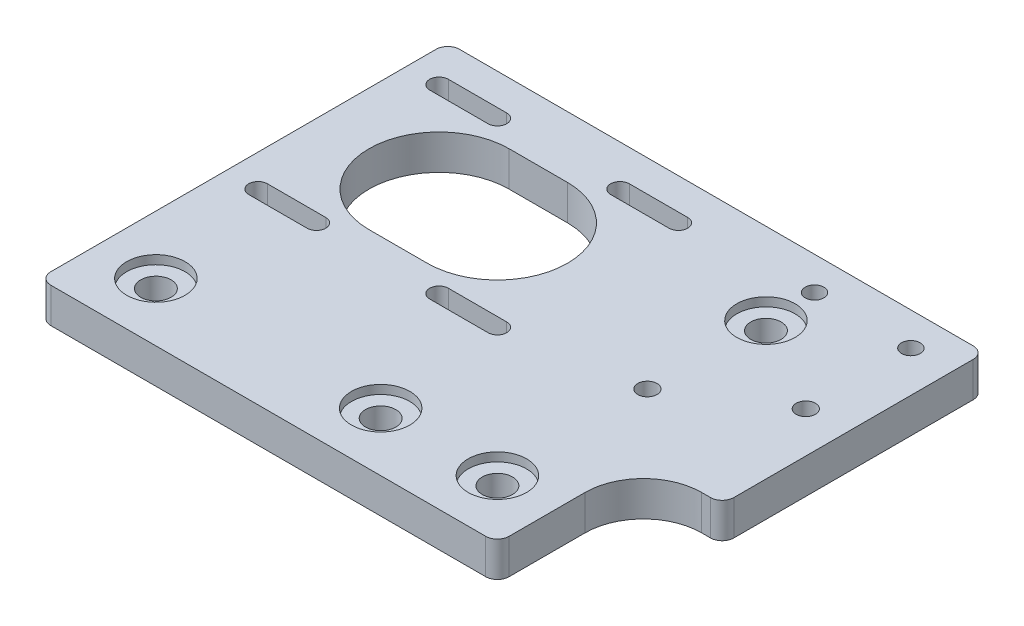
SolidWorks part; units mm, degrees
material "6061 Alloy"
ref_plane "Front" through (0, 0, 0) normal (0, 0, 1) x (1, 0, 0)
ref_plane "Top" through (0, 0, 0) normal (0, 1, 0) x (1, 0, 0)
ref_plane "Right" through (0, 0, 0) normal (1, 0, 0) x (0, 0, -1)
sketch "Sketch3" plane through (0, 0, 0) normal (0, 1, 0) x (1, 0, 0)
  line L0 (20, 70) -> (20, 20) construction
  line L1 (0, 0) -> (78.5, 0)
  line L2 (0, 0) -> (0, 70) construction
  line L3 (0, 70) -> (78.5, 70)
  line L4 (78.5, 0) -> (78.5, 70)
  line L5 (20, 20) -> (78.5, 20) construction
  line L6 (10, 70) -> (10, 10) construction
  line L7 (10, 10) -> (78.5, 10) construction
  line L8 (0, 70) -> (-13.5, 70)
  line L11 (-13.5, 70) -> (-13.5, 25)
  line L12 (-13.5, 25) -> (0, 25)
  line L14 (47.5, 47.5) -> (57.5, 47.5) construction
  line L15 (47.5, 59.5) -> (57.5, 59.5)
  line L16 (47.5, 35.5) -> (57.5, 35.5)
  line L17 (32, 63) -> (42, 63) construction
  line L18 (37, 32) -> (68, 32) construction
  line L19 (37, 32) -> (37, 63) construction
  line L20 (37, 63) -> (68, 63) construction
  line L21 (68, 32) -> (68, 63) construction
  line L22 (37, 32) -> (68, 63) construction
  line L23 (37, 63) -> (68, 32) construction
  line L24 (32, 64.6) -> (42, 64.6)
  line L25 (32, 61.4) -> (42, 61.4)
  line L26 (63, 63) -> (73, 63) construction
  line L27 (63, 64.6) -> (73, 64.6)
  line L28 (63, 61.4) -> (73, 61.4)
  line L29 (63, 32) -> (73, 32) construction
  line L30 (63, 33.6) -> (73, 33.6)
  line L31 (63, 30.4) -> (73, 30.4)
  line L32 (32, 32) -> (42, 32) construction
  line L33 (32, 33.6) -> (42, 33.6)
  line L34 (32, 30.4) -> (42, 30.4)
  line L35 (24.9094, 47.5) -> (47.5, 47.5) construction
  line L36 (73, 63) -> (78.5, 63) construction
  line L37 (32, 63) -> (20, 63) construction
  line L38 (-6.5, 64.325) -> (-6.5, 46.325) construction
  line L39 (10, 35.7) -> (10, 64.325) construction
  line L40 (10, 64.325) -> (-6.5, 64.325) construction
  line L44 (0, 25) -> (0, 0)
  circle A0 centre (10, 56) radius 2.6
  circle A1 centre (10, 10) radius 2.6
  circle A2 centre (68.5, 10) radius 2.6
  arc A3 (47.5, 59.5) -> (47.5, 35.5) centre (47.5, 47.5) ccw
  arc A4 (57.5, 35.5) -> (57.5, 59.5) centre (57.5, 47.5) ccw
  arc A5 (32, 64.6) -> (32, 61.4) centre (32, 63) ccw
  arc A6 (42, 61.4) -> (42, 64.6) centre (42, 63) ccw
  arc A7 (63, 64.6) -> (63, 61.4) centre (63, 63) ccw
  arc A8 (73, 61.4) -> (73, 64.6) centre (73, 63) ccw
  arc A9 (63, 33.6) -> (63, 30.4) centre (63, 32) ccw
  arc A10 (73, 30.4) -> (73, 33.6) centre (73, 32) ccw
  arc A11 (32, 33.6) -> (32, 30.4) centre (32, 32) ccw
  arc A12 (42, 30.4) -> (42, 33.6) centre (42, 32) ccw
  circle A13 centre (10, 35.7) radius 2.7 construction
  circle A14 centre (-6.5, 46.325) radius 2.7 construction
  circle A15 centre (10, 10) radius 4.5 construction
  circle A16 centre (10, 64.325) radius 1.6 construction
  circle A17 centre (-6.5, 64.325) radius 1.6 construction
  circle A18 centre (30, 10) radius 2.6
  point P21 (52.5, 47.5)
  point P26 (52.5, 47.5)
  point P33 (37, 63)
  point P39 (68, 63)
  point P46 (68, 32)
  point P53 (37, 32)
  dimension "D7" = 5.2
  dimension "D10" = 12
  dimension "D12" = 1.6
  dimension "D15" = 10
  dimension "D17" = 18
  dimension "D18" = 7
  dimension "D20" = 2.35
  dimension "D21" = 5.4
  dimension "D22" = 9
  dimension "D23" = 3.2
  dimension "D25" = 5.5
  dimension "D26" = 20
  dimension "D16" = 10.625
  dimension "D8" = 14
  dimension "D9" = 10.7
  dimension "D1" = 70
  dimension "D2" = 10
  dimension "D3" = 20
  dimension "D4" = 20
  dimension "D5" = 10
  dimension "D6" = 10
  dimension "D11" = 31
  dimension "D13" = 10
  dimension "D14" = 12
  dimension "D19" = 16.5
  dimension "D24" = 22.5
extrude "Boss-Extrude1" add sketch "Sketch3" along normal blind 6
sketch "Sketch5" plane through (0, 6, 0) normal (0, 1, 0) x (1, 0, 0)
  circle A0 centre (10, 56) radius 5
  circle A1 centre (10, 10) radius 5
  circle A2 centre (30, 10) radius 5
  circle A3 centre (68.5, 10) radius 5
  dimension "D1" = 10
fillet "Fillet1" radius 10 1 edges at (0, 3, -25)
sketch "Sketch7" plane through (0, 6, 0) normal (0, 1, 0) x (1, 0, 0)
  line L0 (-6.5, 64.325) -> (10, 64.325) construction
  line L1 (-6.5, 67.325) -> (10, 67.325) construction
  line L2 (-6.5, 61.325) -> (10, 61.325) construction
  arc A0 (-6.5, 67.325) -> (-6.5, 61.325) centre (-6.5, 64.325) ccw construction
  arc A1 (10, 61.325) -> (10, 67.325) centre (10, 64.325) ccw construction
  circle A2 centre (-6.5, 64.325) radius 1.35
  circle A3 centre (10, 64.325) radius 1.35
  point P2 (1.75, 64.325)
  dimension "D1" = 3
  dimension "D2" = 2.7
hole_wizard "M3 Clearance Hole1" positions "Sketch8" profile "Sketch9" hole size "M3" standard "ANSI Metric" end condition through all
sketch "Sketch8" plane through (0, 6, 0) normal (0, 1, 0) x (1, 0, 0)
  point P0 (10, 64.325)
  point P3 (-6.5, 64.325)
sketch "Sketch9" plane through (10, 6, -64.325) normal (1, 0, 0) x (0, 0, 1)
  line L0 (0, 0) -> (0, 6)
  line L1 (0, 6) -> (1.6, 6)
  line L2 (1.6, 6) -> (1.6, 0)
  line L5 (1.6, 0) -> (0, 0)
  line L11 (0, -6.35) -> (0, 107.95) construction
  dimension "Thru Hole Dia." = 3.2
  dimension "Thru Hole Depth" = 6
hole_wizard "M4x0.7 Tapped Hole1" positions "Sketch10" profile "Sketch11" tap size "M4x0.7" standard "ANSI Metric" end condition through all
sketch "Sketch10" plane through (0, 6, 0) normal (0, 1, 0) x (1, 0, 0)
  circle A0 centre (15.65, 30.05) radius 11.5
  point P0 (-6.5, 46.325)
  point P3 (10, 35.7)
  dimension "D3" = 23
  dimension "D1" = 5.65
  dimension "D2" = 5.65
sketch "Sketch11" plane through (-6.5, 6, -46.325) normal (1, 0, 0) x (0, 0, 1)
  line L0 (0, 0) -> (0, 6)
  line L1 (0, 6) -> (1.65, 6)
  line L2 (1.65, 6) -> (1.65, 0)
  line L5 (1.65, 0) -> (0, 0)
  line L11 (0, -6.35) -> (0, 107.95) construction
  dimension "Thru Tap Drill Dia." = 3.3
  dimension "Thru Tap Drill Depth" = 6
cosmetic thread "Hole Thread1" parameters "D2"=4
cosmetic thread "Hole Thread2" parameters "D2"=4
fillet "Fillet2" radius 2 5 edges at (-13.5, 3, -25) (0, 3, 0) (-13.5, 3, -70) (78.5, 3, 0) (78.5, 3, -70)
sketch "Sketch12" plane through (0, 6, 0) normal (0, 1, 0) x (1, 0, 0)
  circle A4 centre (10, 35.7) radius 2.65
  circle A5 centre (-6.5, 46.325) radius 2.65
  circle A6 centre (-6.5, 46.325) radius 5
  circle A7 centre (10, 35.7) radius 5
  dimension "D1" = 10
  dimension "D2" = 5.3
extrude "Counterbore" cut sketch "Sketch5" against normal blind 1.5
mirror "Mirror1" about plane through (78.5, 6, 0) normal (-1, 0, 0) of bodies 118 104
delete or keep bodies "Body-Delete/Keep 1" type delete bodies bodies 118
